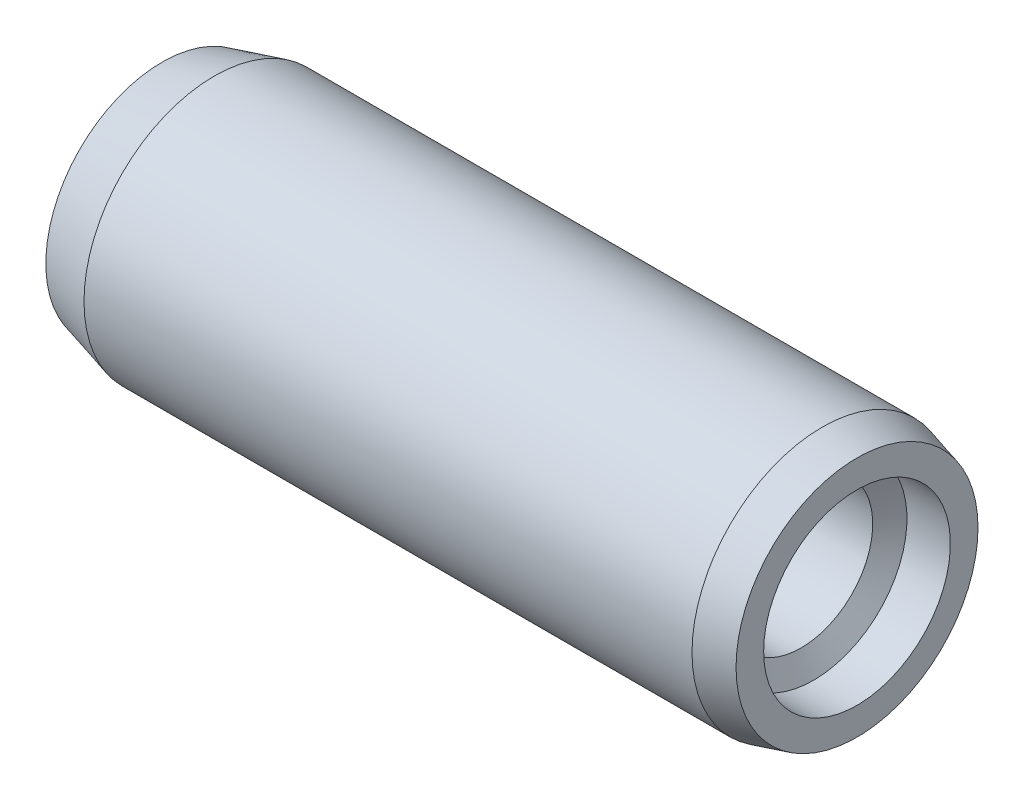
SolidWorks part; units mm, degrees
ref_plane "Front" through (0, 0, 0) normal (0, 0, 1) x (1, 0, 0)
ref_plane "Top" through (0, 0, 0) normal (0, 1, 0) x (1, 0, 0)
ref_plane "Right" through (0, 0, 0) normal (1, 0, 0) x (0, 0, -1)
sketch "Sketch1" plane through (0, 0, 0) normal (0, 0, 1) x (1, 0, 0)
  line L0 (0, 0) -> (0, 2.6785)
  line L1 (0, 2.6785) -> (1.2, 3)
  line L2 (1.2, 3) -> (15.2, 3)
  line L3 (15.2, 3) -> (16, 2.7856)
  line L4 (16, 2.7856) -> (16, 0)
  line L5 (0, 0) -> (-1.8135, 0) construction
  line L6 (16, 0) -> (0, 0)
  dimension "D3" = 15
  dimension "D6" = 75
revolve "Base-Revolve" add sketch "Sketch1" angle 360 about L5
sketch "Sketch2" plane through (0, 0, 0) normal (0, 0, 1) x (1, 0, 0)
  line L0 (16, 2.15) -> (15, 2.15)
  line L2 (16, -2.7856) -> (16, 2.7856) construction
  line L3 (15, 2.15) -> (14.7113, 1.65)
  line L4 (14.7113, 1.65) -> (6, 1.65)
  line L5 (6, 1.65) -> (5.0474, 0)
  line L6 (5.0474, 0) -> (16, 0)
  line L7 (16, 0) -> (16, 2.15)
  line L8 (16, 0) -> (16.5661, 0) construction
  dimension "D4" = 60
  dimension "D6" = 60
revolve "TypeA" cut sketch "Sketch2" angle 360 about L8
cosmetic thread "ThreadCosmetic1" [suppressed] parameters "t1"=6, "d1"=4
sketch "Sketch3" plane through (0, 0, 0) normal (0, 0, 1) x (1, 0, 0)
  line L0 (0, 0) -> (11.3654, 0) construction
  line L1 (9.835, -1.32) -> (10.165, -1.32)
  line L2 (10.165, -1.32) -> (10.165, -1.65)
  line L3 (10.165, -1.65) -> (10, -1.9358)
  line L4 (10, -1.9358) -> (9.835, -1.65)
  line L5 (9.835, -1.32) -> (9.835, -1.65)
  line L6 (16, -2.15) -> (16, 2.15) construction
  dimension "D2" = 3.3
  dimension "D3" = 6
revolve "Cut-Revolve10" [suppressed] cut sketch "Sketch3" angle 360 about L0
pattern_linear "LPattern10" [suppressed] count 13 spacing 0.396 along (1, 0, 0) of bodies 103
equation "\"D1@Sketch3\" =\"D2@Sketch3\" / 10"
equation "\"D2@Sketch3\" = \"d0@Sketch2\""
equation "\"D3@Sketch3\" = \"t1@ThreadCosmetic1\""
equation "\"D3@LPattern10\" = \"D1@Sketch3\"*1.2"
equation "\"D1@LPattern10\" = (  \"t1@ThreadCosmetic1\"  - \"a@Sketch1\" ) / \"D3@LPattern10\""
